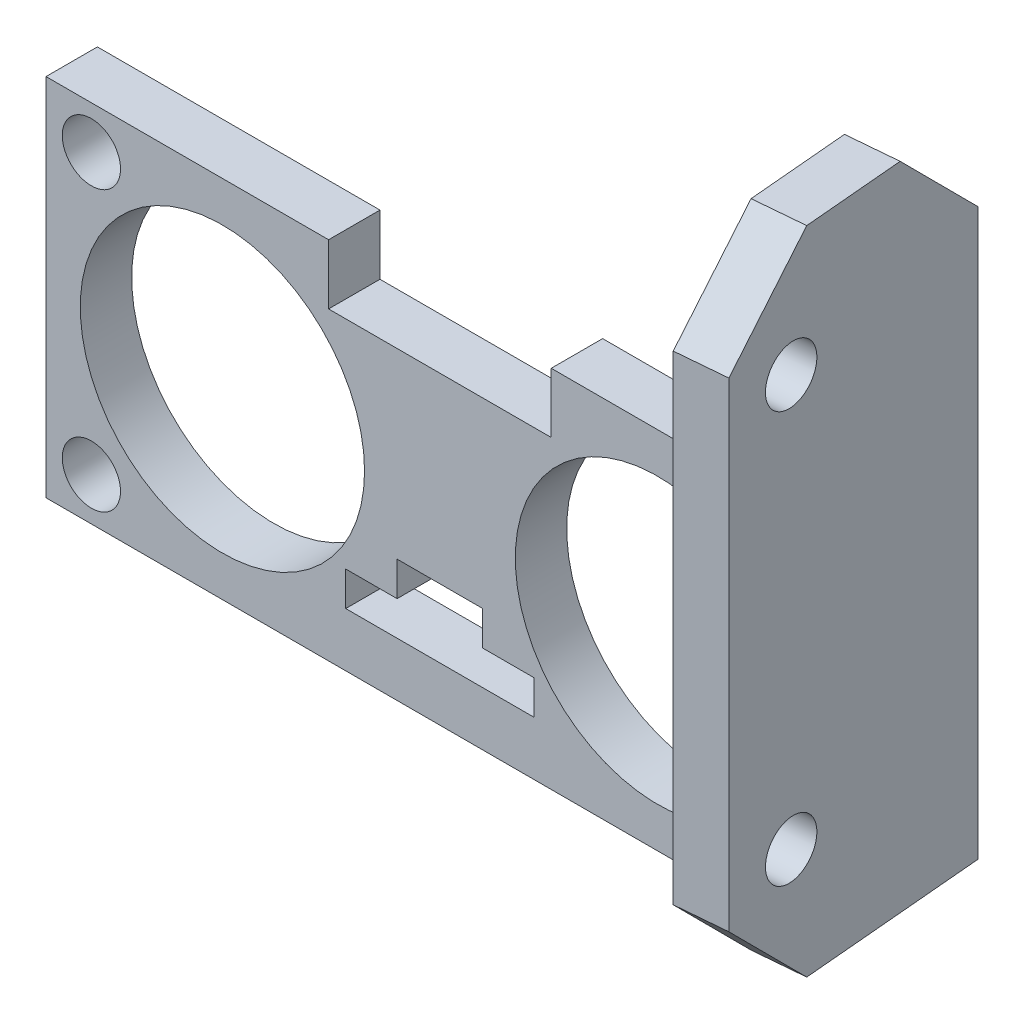
SolidWorks part; units mm, degrees
material "ABS"
ref_plane "前基準面" through (0, 0, 0) normal (0, 0, 1) x (1, 0, 0)
ref_plane "上基準面" through (0, 0, 0) normal (0, 1, 0) x (1, 0, 0)
ref_plane "右基準面" through (0, 0, 0) normal (1, 0, 0) x (0, 0, -1)
sketch "草圖1" plane through (0, 0, 0) normal (0, 0, 1) x (1, 0, 0)
  line L1 (-23, -10.65) -> (23, -10.65)
  line L2 (-23, -10.65) -> (-23, 10.65)
  line L3 (-23, 10.65) -> (23, 10.65)
  line L4 (23, -10.65) -> (23, 10.65)
  line L5 (-23, -10.65) -> (23, 10.65) construction
  line L6 (-23, 10.65) -> (23, -10.65) construction
  point P0 (0, 0)
  dimension "D1" = 46
  dimension "D2" = 21.3
extrude "填料-伸長1" add sketch "草圖1" along normal blind 3
sketch "草圖2" plane through (0, 0, 3) normal (0, 0, 1) x (1, 0, 0)
  line L0 (-12.7, 0) -> (12.7, 0) construction
  circle A0 centre (-12.7, 0) radius 8.3
  circle A1 centre (12.7, 0) radius 8.3
  point P4 (0, 0)
  dimension "D1" = 25.4
  dimension "D2" = 16.6
extrude "除料-伸長1" cut sketch "草圖2" against normal through all
sketch "草圖3" plane through (0, 0, 3) normal (0, 0, 1) x (1, 0, 0)
  line L0 (0, 0) -> (0, 9.15) construction
  line L1 (23, 10.65) -> (-23, 10.65) construction
  line L2 (-4, 7.65) -> (4, 7.65)
  line L3 (-4, 7.65) -> (-4, 10.65)
  line L4 (-4, 10.65) -> (4, 10.65)
  line L5 (4, 7.65) -> (4, 10.65)
  line L6 (-4, 7.65) -> (4, 10.65) construction
  line L7 (-4, 10.65) -> (4, 7.65) construction
  dimension "D1" = 8
  dimension "D2" = 3
extrude "除料-伸長2" cut sketch "草圖3" against normal through all
sketch "草圖4" plane through (0, 0, 3) normal (0, 0, 1) x (1, 0, 0)
  line L0 (0, 0) -> (0, -5.5) construction
  line L2 (-2.5, -3.5) -> (2.5, -3.5)
  line L3 (-2.5, -3.5) -> (-2.5, -7.5)
  line L4 (-2.5, -7.5) -> (2.5, -7.5)
  line L5 (2.5, -3.5) -> (2.5, -7.5)
  line L6 (-2.5, -3.5) -> (2.5, -7.5) construction
  line L7 (-2.5, -7.5) -> (2.5, -3.5) construction
  dimension "D1" = 5
  dimension "D2" = 4
  dimension "D3" = 5.5
extrude "除料-伸長3" cut sketch "草圖4" against normal through all
sketch "草圖5" plane through (0, 0, 3) normal (0, 0, 1) x (1, 0, 0)
  line L0 (0, 0) -> (0, 8.65) construction
  line L1 (2.5, -7.5) -> (5.5, -7.5)
  line L2 (2.5, -7.5) -> (2.5, -5.5)
  line L3 (2.5, -5.5) -> (5.5, -5.5)
  line L4 (5.5, -7.5) -> (5.5, -5.5)
  line L5 (-5.5, 8.65) -> (5.5, 8.65) construction
  line L6 (23, 10.65) -> (4, 10.65) construction
  line L7 (-4.5, 10.15) -> (-6.5, 10.15)
  line L8 (-4.5, 10.15) -> (-4.5, 7.15)
  line L9 (-4.5, 7.15) -> (-6.5, 7.15)
  line L10 (-6.5, 10.15) -> (-6.5, 7.15)
  line L11 (-4.5, 10.15) -> (-6.5, 7.15) construction
  line L12 (-4.5, 7.15) -> (-6.5, 10.15) construction
  line L13 (6.5, 10.15) -> (4.5, 10.15)
  line L14 (6.5, 10.15) -> (6.5, 7.15)
  line L15 (6.5, 7.15) -> (4.5, 7.15)
  line L16 (4.5, 10.15) -> (4.5, 7.15)
  line L17 (6.5, 10.15) -> (4.5, 7.15) construction
  line L18 (6.5, 7.15) -> (4.5, 10.15) construction
  line L20 (-2.5, -7.5) -> (-5.5, -7.5)
  line L21 (-2.5, -7.5) -> (-2.5, -5.5)
  line L22 (-2.5, -5.5) -> (-5.5, -5.5)
  line L23 (-5.5, -7.5) -> (-5.5, -5.5)
  point P10 (0, 8.65)
  dimension "D1" = 2
  dimension "D2" = 3
  dimension "D3" = 2
  dimension "D4" = 3
  dimension "D5" = 11
  dimension "D6" = 0.5
extrude "除料-伸長4" cut sketch "草圖5" against normal blind 1
hole_wizard "M3 餘隙孔1" positions "草圖6" profile "草圖7" hole size "M3" standard "Ansi Metric" end condition through all
sketch "草圖6" plane through (0, 0, 3) normal (0, 0, 1) x (1, 0, 0)
  line L1 (-20.35, -8.15) -> (20.35, -8.15) construction
  line L2 (-20.35, -8.15) -> (-20.35, 8.15) construction
  line L3 (-20.35, 8.15) -> (20.35, 8.15) construction
  line L4 (20.35, -8.15) -> (20.35, 8.15) construction
  line L5 (-20.35, -8.15) -> (20.35, 8.15) construction
  line L6 (-20.35, 8.15) -> (20.35, -8.15) construction
  point P1 (20.35, 8.15)
  point P112 (-20.35, -8.15)
  point P113 (-20.35, 8.15)
  point P114 (20.35, -8.15)
  point P118 (0, 0)
  dimension "D1" = 16.3
  dimension "D2" = 40.7
sketch "草圖7" plane through (20.35, 8.15, 3) normal (1, 0, 0) x (0, -1, 0)
  line L0 (0, 0) -> (0, 3)
  line L1 (0, 3) -> (1.7, 3)
  line L2 (1.7, 3) -> (1.7, 0)
  line L5 (1.7, 0) -> (0, 0)
  line L11 (0, -6.35) -> (0, 107.95) construction
  dimension "貫穿孔直徑" = 3.4
  dimension "貫穿孔深度" = 3
sketch "Sketch4" plane through (0, 0, 3) normal (0, 0, 1) x (1, 0, 0)
  line L0 (6.5, 7.15) -> (6.5, 10.15) construction
  line L1 (-5.5, -7.5) -> (5.5, -7.5)
  line L2 (-5.5, -7.5) -> (-5.5, -5.5)
  line L3 (-5.5, -5.5) -> (5.5, -5.5)
  line L4 (5.5, -7.5) -> (5.5, -5.5)
  line L5 (-6.5, 7.15) -> (6.5, 7.15)
  line L6 (-6.5, 7.15) -> (-6.5, 10.65)
  line L7 (-6.5, 10.65) -> (6.5, 10.65)
  line L8 (6.5, 7.15) -> (6.5, 10.65)
  line L10 (23, 10.65) -> (4, 10.65) construction
extrude "Cut-Extrude3" cut sketch "Sketch4" against normal through all
sketch "Sketch5" plane through (0, -10.65, 0) normal (0, -1, 0) x (-1, 0, 0)
  line L0 (-23, 0) -> (-23, -3)
  line L3 (-23, -3) -> (-23.2625, -3)
  line L4 (-23.2625, -3) -> (-23, 0)
  line L5 (-23, -3) -> (-23, 0) construction
  point P4 (0, 0)
  point P5 (0, 0)
  point P6 (-28, -0.4857)
  point P7 (0, 0)
  point P8 (0, 0)
  point P13 (-25, -2.3883)
  point P15 (0, 0)
  point P16 (0, 0)
  point P18 (-23, -0.2444)
  dimension "D1" = 5
extrude "Boss-Extrude2" add sketch "Sketch5" against normal up to surface (21.3 mm away) up to face at (14.75, 10.65, 1.5)
sketch "Sketch7" plane through (22.8253, 0, -1.997) normal (0.9962, 0, -0.0872) x (-0.0872, 0, -0.9962)
  line L1 (-5.016, -10.65) -> (-2.0046, -10.65)
  line L2 (-5.016, -10.65) -> (-5.016, 10.65)
  line L3 (-5.016, 10.65) -> (-2.0046, 10.65)
  line L4 (-2.0046, -10.65) -> (-2.0046, 10.65)
  line L5 (-5.016, 10.65) -> (-2.0046, 10.65) construction
  line L6 (-2.0046, -10.65) -> (-2.0046, 10.65) construction
extrude "Boss-Extrude3" add sketch "Sketch7" along normal blind 2
sketch "Sketch10" plane through (0.4372, 0, 4.997) normal (0.0872, 0, 0.9962) x (0.9962, 0, -0.0872)
  line L0 (22.9125, 10.65) -> (24.9125, 10.65)
  line L1 (22.9125, 10.65) -> (22.9125, 39.35)
  line L2 (24.9125, 10.65) -> (24.9125, 39.35)
  line L3 (22.9125, 39.35) -> (24.9125, 39.35)
  line L4 (24.9125, -10.65) -> (22.9125, -10.65) construction
  dimension "D1" = 50
extrude "Boss-Extrude5" add sketch "Sketch10" against normal up to surface (3.0115 mm away) up to face at (23.9962, 0, -0.0872)
sketch "Sketch12" plane through (0.4372, 0, 4.997) normal (0.0872, 0, 0.9962) x (0.9962, 0, -0.0872)
  line L0 (22.9125, 10.65) -> (22.9125, -10.65)
  line L1 (22.9125, 10.65) -> (24.9125, 16.145)
  line L2 (22.9125, -10.65) -> (24.9125, -5.155)
  line L3 (24.9125, 16.145) -> (24.9125, -5.155)
  line L4 (24.9125, 39.35) -> (24.9125, -10.65) construction
  line M6 (22.9125, -10.65) -> (24.9125, -10.65)
  line M7 (24.9125, -10.65) -> (24.9125, 39.35)
  line M8 (24.9125, 39.35) -> (22.9125, 39.35)
  line M12 (22.9125, 39.35) -> (22.9125, 10.65)
  dimension "D1" = 20
extrude "Cut-Extrude6" cut sketch "Sketch12" against normal through all contours L2 M6 M7 | L1 M12 M7 M8
sketch "Sketch14" plane through (24.8177, 0, -2.1713) normal (0.9962, 0, -0.0872) x (-0.0872, 0, -0.9962)
  line L1 (-2.0046, -5.155) -> (-18.0046, -5.155)
  line L2 (-2.0046, -5.155) -> (-2.0046, 32.845)
  line L3 (-2.0046, 32.845) -> (-18.0046, 32.845)
  line L4 (-18.0046, -5.155) -> (-18.0046, 32.845)
  dimension "D1" = 16
  dimension "D2" = 38
extrude "Boss-Extrude8" add sketch "Sketch14" along normal blind 3
chamfer "Chamfer2" distance 2 angle 45 1 edges at (25.2549, 5.495, 2.8257)
sketch "Sketch15" plane through (24.8177, 0, -2.1713) normal (-0.9962, 0, 0.0872) x (0.0872, 0, 0.9962)
  line L0 (18.0046, 13.845) -> (14.0046, 13.845) construction
  line L1 (18.0046, 32.845) -> (18.0046, -5.155) construction
  line L2 (14.0046, 25.845) -> (14.0046, 1.845) construction
  circle A0 centre (14.0046, 25.845) radius 1.65
  circle A1 centre (14.0046, 1.845) radius 1.65
  point P7 (14.0046, 13.845)
  dimension "D2" = 3.3
  dimension "D1" = 4
  dimension "D3" = 24
extrude "Cut-Extrude7" cut sketch "Sketch15" against normal through all
chamfer "Chamfer3" distance 5 angle 45 3 edges at (26.4867, 32.845, -0.305) (27.8812, 32.845, 15.6341) (27.8812, -5.155, 15.6341)
